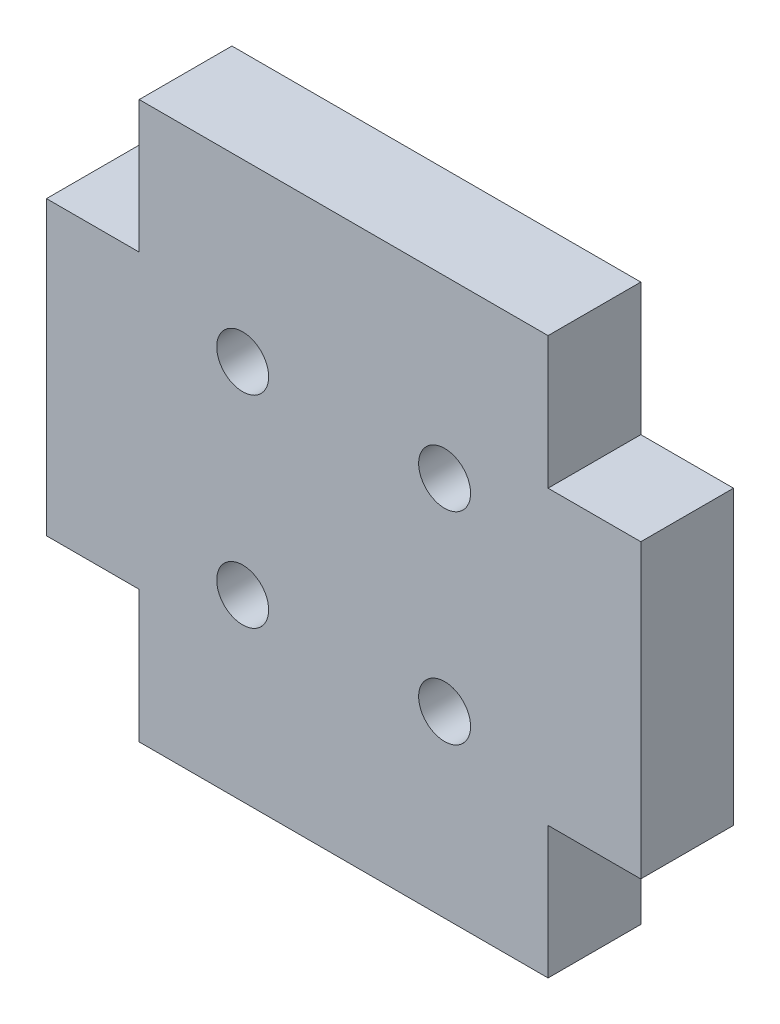
SolidWorks part; units mm, degrees
material "ABS"
ref_plane "Plan de face" through (0, 0, 0) normal (0, 0, 1) x (1, 0, 0)
ref_plane "Plan de dessus" through (0, 0, 0) normal (0, 1, 0) x (1, 0, 0)
ref_plane "Plan de droite" through (0, 0, 0) normal (1, 0, 0) x (0, 0, -1)
sketch "Esquisse1" plane through (0, 0, 0) normal (0, 0, 1) x (1, 0, 0)
  line L1 (-14, 19.05) -> (14, 19.05)
  line L2 (-14, 19.05) -> (-14, -19.05)
  line L3 (-14, -19.05) -> (14, -19.05)
  line L4 (14, 19.05) -> (14, -19.05)
  line L5 (-20.35, 10) -> (20.35, 10)
  line L6 (-20.35, 10) -> (-20.35, -10)
  line L7 (-20.35, -10) -> (20.35, -10)
  line L8 (20.35, 10) -> (20.35, -10)
  point P8 (0, 10)
  point P11 (-20.35, 0)
  point P12 (0, 19.05)
  point P13 (-14, 0)
  dimension "D1" = 28
  dimension "D2" = 6.35
  dimension "D3" = 20
  dimension "D4" = 38.1
extrude "Boss.-Extru.1" add sketch "Esquisse1" along normal blind 6.35 contours L2 L7 L4 L5 | L6 L7 L2 L5 | L7 L2 L3 L4 | L8 L5 L4 L7 | L2 L5 L4 L1 region at (0, 14.525, 0) region at (0, 0, 0) region at (-17.175, 0, 0) region at (17.175, 0, 0) region at (0, -14.525, 0)
sketch "Esquisse2" plane through (0, 0, 6.35) normal (0, 0, 1) x (1, 0, 0)
  circle A0 centre (-6.9148, 7.0418) radius 1.778
  circle A1 centre (6.9148, 7.0418) radius 1.778
  circle A2 centre (6.9148, -6.7878) radius 1.778
  circle A3 centre (-6.9148, -6.7878) radius 1.778
  dimension "D1" = 3.556
  dimension "D2" = 3.556
  dimension "D3" = 3.556
  dimension "D4" = 3.556
extrude "Enlèv. mat.-Extru.1" cut sketch "Esquisse2" against normal up to next
